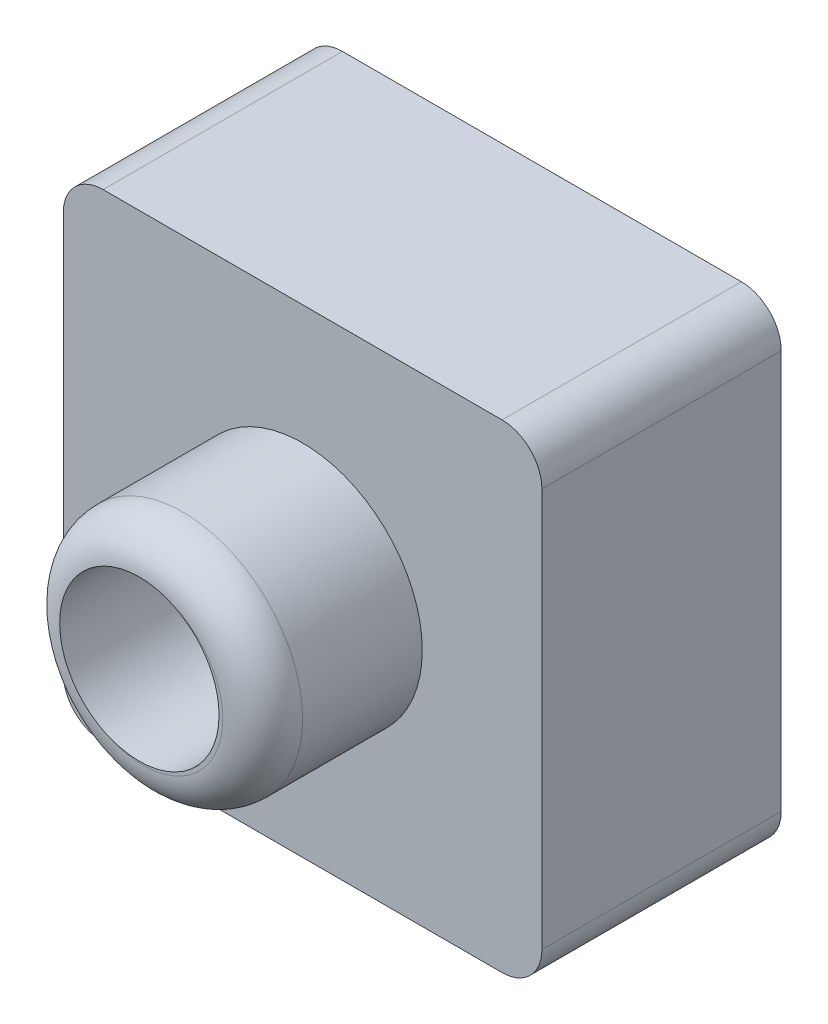
SolidWorks part; units mm, degrees
ref_plane "Front Plane" through (0, 0, 0) normal (0, 0, 1) x (1, 0, 0)
ref_plane "Top Plane" through (0, 0, 0) normal (0, 1, 0) x (1, 0, 0)
ref_plane "Right Plane" through (0, 0, 0) normal (1, 0, 0) x (0, 0, -1)
sketch "Sketch2" plane through (0, 0, 0) normal (0, 0, 1) x (1, 0, 0)
  line L1 (0, -1178.1784) -> (3048, -1178.1784)
  line L2 (0, -1178.1784) -> (0, 1869.8216)
  line L3 (0, 1869.8216) -> (3048, 1869.8216)
  line L4 (3048, -1178.1784) -> (3048, 1869.8216)
  dimension "D1" = 3048
  dimension "D2" = 3048
extrude "Boss-Extrude1" add sketch "Sketch2" along normal blind 1524
sketch "Sketch3" plane through (0, 0, 1524) normal (0, 0, 1) x (1, 0, 0)
  line L0 (0, 1869.8216) -> (0, -1178.1784) construction
  line L1 (3048, 1869.8216) -> (0, 1869.8216) construction
  circle A0 centre (1524, 345.8216) radius 762
  dimension "D1" = 1524
  dimension "D2" = 1524
  dimension "D3" = 1524
extrude "Boss-Extrude2" add sketch "Sketch3" along normal blind 1016
sketch "Sketch8" plane through (0, 0, 2540) normal (0, 0, 1) x (1, 0, 0)
  circle A0 centre (1500.0651, 356.4593) radius 508
  dimension "D1" = 1016
extrude "Cut-Extrude1" cut sketch "Sketch8" against normal through all both and the other way through all
fillet "Fillet1" radius 254 5 edges at (2286, 345.8216, 2540) (3048, -1178.1784, 762) (3048, 1869.8216, 762) (0, -1178.1784, 762) (0, 1869.8216, 762)
shell "Shell1" thickness 50.8 removed face at (2008.0651, 356.4593, 0)
